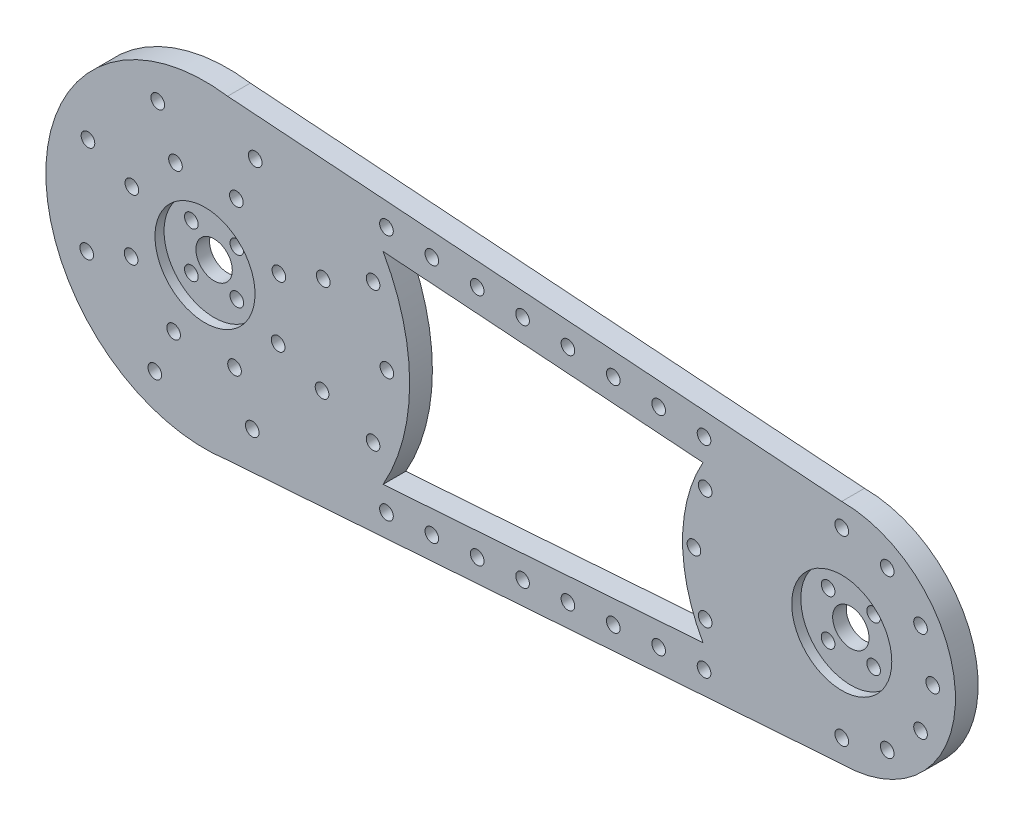
SolidWorks part; units mm, degrees
ref_plane "前视基准面" through (0, 0, 0) normal (0, 0, 1) x (1, 0, 0)
ref_plane "上视基准面" through (0, 0, 0) normal (0, 1, 0) x (1, 0, 0)
ref_plane "右视基准面" through (0, 0, 0) normal (1, 0, 0) x (0, 0, -1)
other "Configuration Table"
sketch "草图1" plane through (0, 0, 0) normal (0, 0, 1) x (1, 0, 0)
  line L0 (0, 0) -> (140, 0)
  line L1 (0, 35) -> (140, 25)
  line L2 (0, -35) -> (140, -25)
  circle A0 centre (0, 0) radius 35
  circle A1 centre (140, 0) radius 25
  dimension "D1" = 70
  dimension "D3" = 50
  dimension "D2" = 140
extrude "凸台-拉伸3" add sketch "草图1" along normal blind 5 contours A0 L1 L2 | A1 L0 A0 L2 | A1 L1 A0 L0 | A1 region at (72.7482, 16.0498, 0) region at (-0.0004, 0, 0) region at (72.7482, -16.0498, 0) region at (122.8223, 17.1777, 0)
sketch "草图4" plane through (0, 0, 5) normal (0, 0, 1) x (1, 0, 0)
  line L1 (-5, -5) -> (5, -5)
  line L2 (-5, -5) -> (-5, 5)
  line L3 (-5, 5) -> (5, 5)
  line L4 (5, -5) -> (5, 5)
  line L5 (-5, -5) -> (5, 5) construction
  line L6 (-5, 5) -> (5, -5) construction
  line L7 (135, -5) -> (145, -5)
  line L8 (135, -5) -> (135, 5)
  line L9 (135, 5) -> (145, 5)
  line L10 (145, -5) -> (145, 5)
  line L11 (135, -5) -> (145, 5) construction
  line L12 (135, 5) -> (145, -5) construction
  circle A0 centre (0, 0) radius 4
  circle A1 centre (-5, 5) radius 1.5
  circle A2 centre (5, 5) radius 1.5
  circle A3 centre (5, -5) radius 1.5
  circle A4 centre (-5, -5) radius 1.5
  circle A5 centre (140, 0) radius 4
  circle A6 centre (135, 5) radius 1.5
  circle A7 centre (145, 5) radius 1.5
  circle A8 centre (145, -5) radius 1.5
  circle A9 centre (135, -5) radius 1.5
  dimension "D1" = 8
  dimension "D4" = 3
  dimension "D6" = 8
  dimension "D9" = 3
  dimension "D2" = 10
  dimension "D3" = 10
  dimension "D7" = 10
  dimension "D8" = 10
  dimension "D5" = 4
  dimension "D10" = 4
extrude "切除-拉伸3" cut sketch "草图4" against normal blind 5 contours A5 | A0 | L2 A4 L1 | L1 A4 L2 | A6 | A9 | A8 | A7 | A1 | A2 | A3 region at (-4.3634, -4.3634, 5) region at (-5.2122, -5.2122, 5) region at (0, 0, 5) region at (140, 0, 5)
sketch "草图5" plane through (0, 0, 5) normal (0, 0, 1) x (1, 0, 0)
  circle A0 centre (0, 0) radius 11
  circle A1 centre (140, 0) radius 11
  dimension "D1" = 22
  dimension "D2" = 22
extrude "切除-拉伸4" cut sketch "草图5" against normal blind 2
sketch "草图6" plane through (0, 0, 5) normal (0, 0, 1) x (1, 0, 0)
  circle A0 centre (0, 0) radius 30
  circle A1 centre (0, 30) radius 1.5
  circle A2 centre (15, 25.9808) radius 1.5
  circle A3 centre (25.9808, 15) radius 1.5
  circle A4 centre (30, 0) radius 1.5
  circle A5 centre (25.9808, -15) radius 1.5
  circle A6 centre (15, -25.9808) radius 1.5
  circle A7 centre (0, -30) radius 1.5
  circle A8 centre (-15, -25.9808) radius 1.5
  circle A9 centre (-25.9808, -15) radius 1.5
  circle A10 centre (-30, 0) radius 1.5
  circle A11 centre (-25.9808, 15) radius 1.5
  circle A12 centre (-15, 25.9808) radius 1.5
  circle A13 centre (140, 0) radius 20
  circle A14 centre (140, 20) radius 1.5
  circle A15 centre (150, 17.3205) radius 1.5
  circle A16 centre (157.3205, 10) radius 1.5
  circle A17 centre (160, 0) radius 1.5
  circle A18 centre (157.3205, -10) radius 1.5
  circle A19 centre (150, -17.3205) radius 1.5
  circle A20 centre (140, -20) radius 1.5
  circle A21 centre (130, -17.3205) radius 1.5
  circle A22 centre (122.6795, -10) radius 1.5
  circle A23 centre (120, 0) radius 1.5
  circle A24 centre (122.6795, 10) radius 1.5
  circle A25 centre (130, 17.3205) radius 1.5
  point P29 (0, 0)
  dimension "D1" = 60
  dimension "D2" = 3
  dimension "D4" = 40
  dimension "D5" = 3
  dimension "D3" = 12
  dimension "D6" = 12
extrude "切除-拉伸6" cut sketch "草图6" against normal through all contours A0 A12 | A11 | A12 | A1 | A2 | A3 | A4 | A5 | A6 | A7 | A8 | A9 | A10 | A25 | A14 | A15 | A16 | A17 | A18 | A19 | A20 | A21 | A22 | A23 | A24 region at (-14.6783, 25.4236, 5)
sketch "草图8" plane through (0, 0, 5) normal (0, 0, 1) x (1, 0, 0)
  line L4 (-0.1715, -29.9995) -> (139.8316, -19.9993)
  line L5 (139.8316, 19.9993) -> (-0.1715, 29.9995)
  line L6 (-0.1715, -29.9995) -> (139.8316, -19.9993)
  line L7 (139.8316, 19.9993) -> (-0.1715, 29.9995)
  line L8 (-0.7125, 25.0254) -> (139.2875, 15.0254)
  line L9 (-0.7125, 25.0254) -> (139.2875, 15.0254)
  line L11 (-0.7125, -25.0254) -> (139.2875, -15.0254)
  line L12 (-0.7125, -25.0254) -> (139.2875, -15.0254)
  circle A3 centre (0, 30) radius 1.5
  arc A4 (139.8316, -19.9993) -> (139.8316, 19.9993) centre (140, 0) ccw
  arc A5 (-0.1715, 29.9995) -> (-0.1715, -29.9995) centre (0, 0) ccw
  arc A6 (139.8316, -19.9993) -> (139.8316, 19.9993) centre (140, 0) ccw
  arc A7 (-0.1715, 29.9995) -> (-0.1715, -29.9995) centre (0, 0) ccw
  circle A8 centre (9.9746, 29.2875) radius 1.5
  circle A9 centre (19.9492, 28.5751) radius 1.5
  circle A10 centre (29.9238, 27.8626) radius 1.5
  circle A11 centre (39.8983, 27.1501) radius 1.5
  circle A12 centre (49.8729, 26.4376) radius 1.5
  circle A13 centre (59.8475, 25.7252) radius 1.5
  circle A14 centre (69.8221, 25.0127) radius 1.5
  circle A15 centre (79.7967, 24.3002) radius 1.5
  circle A16 centre (89.7713, 23.5878) radius 1.5
  circle A17 centre (99.7459, 22.8753) radius 1.5
  circle A18 centre (109.7205, 22.1628) radius 1.5
  circle A19 centre (119.695, 21.4504) radius 1.5
  circle A20 centre (129.6696, 20.7379) radius 1.5
  circle A21 centre (0, -30) radius 1.5
  circle A22 centre (9.9746, -29.2875) radius 1.5
  circle A23 centre (19.9492, -28.5751) radius 1.5
  circle A24 centre (29.9238, -27.8626) radius 1.5
  circle A25 centre (39.8983, -27.1501) radius 1.5
  circle A26 centre (49.8729, -26.4376) radius 1.5
  circle A27 centre (59.8475, -25.7252) radius 1.5
  circle A28 centre (69.8221, -25.0127) radius 1.5
  circle A29 centre (79.7967, -24.3002) radius 1.5
  circle A30 centre (89.7713, -23.5878) radius 1.5
  circle A31 centre (99.7459, -22.8753) radius 1.5
  circle A32 centre (109.7205, -22.1628) radius 1.5
  circle A33 centre (119.695, -21.4504) radius 1.5
  circle A34 centre (129.6696, -20.7379) radius 1.5
  circle A35 centre (0, 0) radius 35
  circle A36 centre (140, 0) radius 25
  dimension "D2" = 14
  dimension "D1" = 5
  dimension "D4" = 10
  dimension "D5" = 10
  dimension "D3" = 14
extrude "切除-拉伸8" cut sketch "草图8" against normal through all contours A36 L9 A35 L12 | L6 A25 | L6 A25 | A8 | A9 | A10 | A11 | A12 | A13 | A14 | A16 | A15 | A17 | A18 | A19 | A20 | A34 | A33 | A32 | A31 | A30 | A29 | A28 | A27 | A26 | A24 | A23 | A22 region at (72.4357, 0, 5) region at (39.8525, -26.5083, 5) region at (39.9432, -27.7783, 5)
sketch "草图9" plane through (0, 0, 5) normal (0, 0, 1) x (1, 0, 0)
  circle A0 centre (15, 25.9808) radius 1.5
  circle A1 centre (15, -25.9808) radius 1.5
extrude "凸台-拉伸4" add sketch "草图9" against normal blind 5
sketch "草图10" plane through (0, 0, 5) normal (0, 0, 1) x (1, 0, 0)
  circle A0 centre (130, -17.3205) radius 1.5
  circle A1 centre (130, 17.3205) radius 1.5
extrude "凸台-拉伸6" add sketch "草图10" against normal blind 5
sketch "草图11" plane through (0, 0, 5) normal (0, 0, 1) x (1, 0, 0)
  circle A0 centre (25.9808, -15) radius 1.5
  circle A1 centre (30, 0) radius 1.5
  circle A2 centre (25.9808, 15) radius 1.5
  circle A3 centre (122.6795, -10) radius 1.5
  circle A4 centre (120, 0) radius 1.5
  circle A5 centre (122.6795, 10) radius 1.5
  circle A6 centre (119.695, 21.4504) radius 1.5
  circle A7 centre (119.695, -21.4504) radius 1.5
  circle A8 centre (29.9238, -27.8626) radius 1.5
  circle A9 centre (29.9238, 27.8626) radius 1.5
  circle A10 centre (0, 0) radius 11
  circle A11 centre (0, 0) radius 35
  circle A12 centre (19.9492, -28.5751) radius 1.5
  circle A13 centre (19.9492, 28.5751) radius 1.5
  circle A14 centre (140, 0) radius 11
  circle A15 centre (140, 0) radius 24.9365
  circle A16 centre (129.6696, -20.7379) radius 1.5
  circle A17 centre (129.6696, 20.7379) radius 1.5
extrude "凸台-拉伸12" add sketch "草图11" against normal blind 5 contours A16 | A7 | A6 | A13 A11 A12 A0 A1 A2 A10 | A1 | A2 | A11 A13 | A11 A13 | A9 | A8 | A17 | A12 | A0 region at (30, 0, 5) region at (25.9808, 15, 5) region at (119.695, 21.4504, 5) region at (119.695, -21.4504, 5) region at (29.9238, -27.8626, 5) region at (29.9238, 27.8626, 5) region at (30.4854, -15.0772, 5) region at (19.6276, 28.1144, 5) region at (20.3571, 29.1594, 5) region at (129.6696, -20.7379, 5)
sketch "草图14" plane through (0, 0, 0) normal (0, 0, -1) x (-1, 0, 0)
  circle A2 centre (-11.0396, 25.7318) radius 1.5
  circle A3 centre (-6.8997, 16.0824) radius 1.5
  circle A4 centre (6.4931, 16.2508) radius 1.5
  circle A5 centre (10.389, 26.0013) radius 1.5
  circle A6 centre (16.0824, 6.8997) radius 1.5
  circle A7 centre (25.7318, 11.0396) radius 1.5
  circle A8 centre (16.2508, -6.4931) radius 1.5
  circle A9 centre (26.0013, -10.389) radius 1.5
  circle A10 centre (6.8997, -16.0824) radius 1.5
  circle A11 centre (11.0396, -25.7318) radius 1.5
  circle A12 centre (-6.4931, -16.2508) radius 1.5
  circle A13 centre (-10.389, -26.0013) radius 1.5
  circle A14 centre (-16.0824, -6.8997) radius 1.5
  circle A15 centre (-25.7318, -11.0396) radius 1.5
  circle A16 centre (-16.2508, 6.4931) radius 1.5
  circle A17 centre (-26.0013, 10.389) radius 1.5
  point P41 (0, 0)
  dimension "D1" = 8
extrude "切除-拉伸9" cut sketch "草图14" against normal blind 5
sketch "草图15" plane through (0, 0, 0) normal (0, 0, -1) x (-1, 0, 0)
  line L0 (-26.2977, -23.0961) -> (-32.9913, -22.618)
  line L1 (-26.2977, -23.0961) -> (-121.0676, -16.3268) construction
  line L2 (-26.2977, 23.0961) -> (-32.9913, 22.618)
  line L3 (-26.2977, 23.0961) -> (-121.0676, 16.3268) construction
  circle A0 centre (0, 0) radius 35
  circle A1 centre (0, 0) radius 40
  dimension "D1" = 80
extrude "凸台-拉伸13" add sketch "草图15" against normal blind 5 contours L2 A1 L0 A0 region at (29.6102, -22.3765, 0)
sketch "草图16" plane through (0, 0, 0) normal (0, 0, -1) x (-1, 0, 0)
  circle A1 centre (-35, 0) radius 1.5
  circle A2 centre (-32.3358, 13.3939) radius 1.5
  circle A16 centre (-32.3358, -13.3939) radius 1.5
  circle A17 centre (-24.7487, 24.7487) radius 1.5 [skipped]
  circle A18 centre (-24.7487, -24.7487) radius 1.5 [skipped]
  circle A19 centre (-13.3939, -32.3358) radius 1.5 [skipped]
  circle A20 centre (-13.3939, 32.3358) radius 1.5 [skipped]
  circle A21 centre (0, 35) radius 1.5 [skipped]
  circle A22 centre (13.3939, 32.3358) radius 1.5 [skipped]
  circle A23 centre (24.7487, 24.7487) radius 1.5 [skipped]
  circle A24 centre (32.3358, 13.3939) radius 1.5 [skipped]
  circle A25 centre (35, 0) radius 1.5 [skipped]
  circle A26 centre (32.3358, -13.3939) radius 1.5 [skipped]
  circle A27 centre (24.7487, -24.7487) radius 1.5 [skipped]
  circle A28 centre (13.3939, -32.3358) radius 1.5 [skipped]
  circle A29 centre (0, -35) radius 1.5 [skipped]
  dimension "D1" = 3
  dimension "D2" = 16
extrude "切除-拉伸10" cut sketch "草图16" against normal blind 5
sketch "草图18" plane through (0, 0, 5) normal (0, 0, 1) x (1, 0, 0)
  line L0 (32.9913, 22.618) -> (39.1555, 22.1777)
  line L1 (32.9913, 22.618) -> (121.0676, 16.3268) construction
  line L2 (32.9913, -22.618) -> (39.1555, -22.1777)
  line L3 (32.9913, -22.618) -> (121.0676, -16.3268) construction
  circle A0 centre (0, 0) radius 40
  circle A1 centre (0, 0) radius 45
  dimension "D1" = 90
extrude "凸台-拉伸14" add sketch "草图18" against normal blind 5 contours L2 A1 L0 A0 region at (40.3299, 0, 5)
sketch "草图19" plane through (0, 0, 5) normal (0, 0, 1) x (1, 0, 0)
  circle A0 centre (32.3358, 13.3939) radius 1.5
  circle A1 centre (35, 0) radius 1.5
  circle A2 centre (32.3358, -13.3939) radius 1.5
extrude "凸台-拉伸15" add sketch "草图19" against normal blind 5
sketch "草图20" plane through (0, 0, 0) normal (0, 0, -1) x (-1, 0, 0)
  circle A1 centre (-40, 0) radius 1.5
  circle A2 centre (-36.9552, 15.3073) radius 1.5
  circle A4 centre (-15.3073, 36.9552) radius 1.5
  circle A5 centre (0, 40) radius 1.5
  circle A6 centre (15.3073, 36.9552) radius 1.5
  circle A7 centre (28.2843, 28.2843) radius 1.5
  circle A8 centre (36.9552, 15.3073) radius 1.5
  circle A9 centre (40, 0) radius 1.5
  circle A10 centre (36.9552, -15.3073) radius 1.5
  circle A11 centre (28.2843, -28.2843) radius 1.5
  circle A12 centre (15.3073, -36.9552) radius 1.5
  circle A13 centre (0, -40) radius 1.5
  circle A14 centre (-15.3073, -36.9552) radius 1.5
  circle A16 centre (-36.9552, -15.3073) radius 1.5
  circle A17 centre (-28.2843, -28.2843) radius 1.5 [skipped]
  circle A18 centre (-28.2843, 28.2843) radius 1.5 [skipped]
  point P38 (0, 0)
  dimension "D2" = 3
  dimension "D3" = 16
extrude "切除-拉伸11" cut sketch "草图20" against normal blind 5
sketch "草图21" plane through (0, 0, 0) normal (0, 0, -1) x (-1, 0, 0)
  line L0 (-121.0676, 16.3268) -> (-115.113, 16.7522)
  line L1 (-39.1555, 22.1777) -> (-121.0676, 16.3268) construction
  line L2 (-121.0676, -16.3268) -> (-115.113, -16.7522)
  line L3 (-39.1555, -22.1777) -> (-121.0676, -16.3268) construction
  circle A0 centre (-140, 0) radius 25
  circle A1 centre (-140, 0) radius 27.5
  circle A2 centre (-140, 0) radius 30
  dimension "D1" = 50
  dimension "D2" = 55
  dimension "D3" = 60
extrude "凸台-拉伸16" add sketch "草图21" against normal blind 5 contours L2 A1 L0 A0 | L2 A2 L0 A1 region at (119.5259, 16.0943, 0) region at (116.5483, 16.3042, 0)
sketch "草图22" plane through (0, 0, 5) normal (0, 0, 1) x (1, 0, 0)
  circle A1 centre (122.6795, 10) radius 1.5
  circle A2 centre (120, 0) radius 1.5
  circle A3 centre (122.6795, -10) radius 1.5
extrude "凸台-拉伸17" add sketch "草图22" against normal blind 5
sketch "草图23" plane through (0, 0, 5) normal (0, 0, 1) x (1, 0, 0)
  circle A0 centre (140, 0) radius 27.5
  circle A1 centre (112.5, 0) radius 1.5
  circle A2 centre (116.1843, 13.75) radius 1.5
  circle A4 centre (140, 27.5) radius 1.5
  circle A5 centre (153.75, 23.8157) radius 1.5
  circle A6 centre (163.8157, 13.75) radius 1.5
  circle A7 centre (167.5, 0) radius 1.5
  circle A8 centre (163.8157, -13.75) radius 1.5
  circle A9 centre (153.75, -23.8157) radius 1.5
  circle A10 centre (140, -27.5) radius 1.5
  circle A12 centre (116.1843, -13.75) radius 1.5
  circle A13 centre (126.25, 23.8157) radius 1.5 [skipped]
  circle A14 centre (126.25, -23.8157) radius 1.5 [skipped]
  dimension "D1" = 55
  dimension "D2" = 3
  dimension "D3" = 12
extrude "切除-拉伸15" cut sketch "草图23" against normal blind 5 contours A0 A2 | A0 A12 | A0 A12 | A1 | A2 region at (115.6394, 14.0646, 5) region at (115.6394, -14.0646, 5) region at (116.742, -13.428, 5)
sketch "草图24" plane through (0, 0, 5) normal (0, 0, 1) x (1, 0, 0)
  circle A0 centre (116.1843, 13.75) radius 1.5
  circle A1 centre (112.5, 0) radius 1.5
  circle A2 centre (116.1843, -13.75) radius 1.5
extrude "凸台-拉伸21" add sketch "草图24" against normal blind 5
sketch "草图29" plane through (0, 0, 5) normal (0, 0, 1) x (1, 0, 0)
  line L0 (115.113, 16.7522) -> (109.4918, 17.1537)
  line L1 (39.1555, 22.1777) -> (115.113, 16.7522) construction
  line L2 (115.113, -16.7522) -> (109.4918, -17.1537)
  line L3 (39.1555, -22.1777) -> (115.113, -16.7522) construction
  circle A0 centre (140, 0) radius 35
  circle A1 centre (140, 0) radius 30
  circle A2 centre (140, 0) radius 32.5
  circle A3 centre (107.5, 0) radius 1.5
  circle A4 centre (109.9739, 12.4372) radius 1.5
  circle A5 centre (117.019, 22.981) radius 1.5
  circle A6 centre (127.5628, 30.0261) radius 1.5
  circle A7 centre (140, 32.5) radius 1.5
  circle A8 centre (152.4372, 30.0261) radius 1.5
  circle A9 centre (162.981, 22.981) radius 1.5
  circle A10 centre (170.0261, 12.4372) radius 1.5
  circle A11 centre (172.5, 0) radius 1.5
  circle A12 centre (170.0261, -12.4372) radius 1.5
  circle A13 centre (162.981, -22.981) radius 1.5
  circle A14 centre (152.4372, -30.0261) radius 1.5
  circle A15 centre (140, -32.5) radius 1.5
  circle A16 centre (127.5628, -30.0261) radius 1.5
  circle A17 centre (117.019, -22.981) radius 1.5
  circle A18 centre (109.9739, -12.4372) radius 1.5
  dimension "D1" = 70
  dimension "D2" = 65
  dimension "D3" = 3
  dimension "D4" = 16
extrude "凸台-拉伸22" add sketch "草图29" against normal blind 5 contours A18 A2 L2 A1 L0 A4 A3 | A18 A2 A3 A4 L0 A0 L2 region at (109.6525, 0, 5) region at (111.0744, 15.5717, 5)
